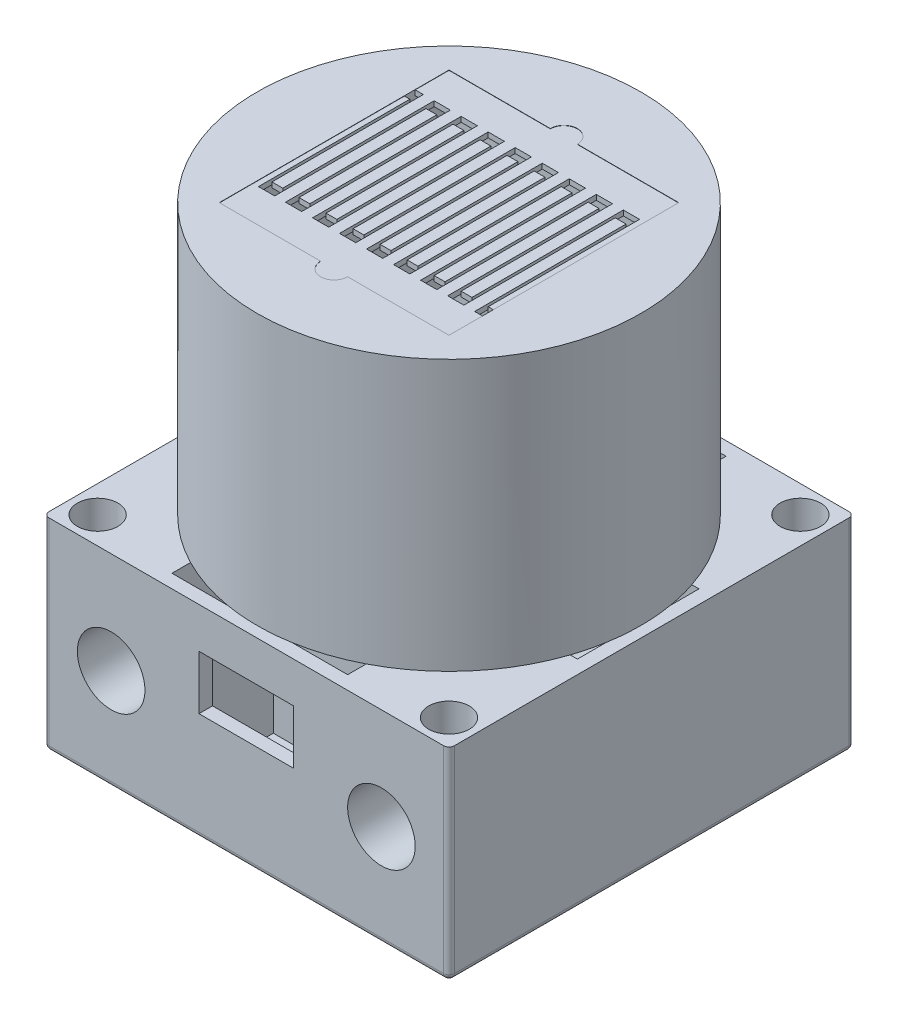
SolidWorks part; units mm, degrees
note: The reader was unsure of these and kept them because the rebuilt part matched: shared geometry of "草图9<2>".
ref_plane "前视基准面" through (0, 0, 0) normal (0, 0, 1) x (1, 0, 0)
ref_plane "上视基准面" through (0, 0, 0) normal (0, 1, 0) x (1, 0, 0)
ref_plane "右视基准面" through (0, 0, 0) normal (1, 0, 0) x (0, 0, -1)
sketch "草图2" plane through (0, 0, 0) normal (0, 1, 0) x (1, 0, 0)
  line L1 (-7.5, -7.5) -> (7.5, -7.5)
  line L2 (-7.5, -7.5) -> (-7.5, 7.5)
  line L3 (-7.5, 7.5) -> (7.5, 7.5)
  line L4 (7.5, -7.5) -> (7.5, 7.5)
extrude "凸台-拉伸1" add sketch "草图2" along normal blind 7.5
sketch "草图3" plane through (0, 7.5, 0) normal (0, 1, 0) x (-1, 0, 0)
  line L1 (7, 2.25) -> (-7, 2.25)
  line L2 (7, 2.25) -> (7, -2.25)
  line L3 (7, -2.25) -> (-7, -2.25)
  line L4 (-7, 2.25) -> (-7, -2.25)
extrude "切除-拉伸1" cut sketch "草图3" against normal blind 7
sketch "草图4" plane through (0, 7.5, 0) normal (0, 1, 0) x (1, 0, 0)
  circle A0 centre (0, 0) radius 3
extrude "切除-拉伸2" cut sketch "草图4" against normal blind 4.5
sketch "草图5" plane through (0, 7.5, 0) normal (0, 1, 0) x (-1, 0, 0)
  line L0 (7.9075, 0) -> (-8.3479, 0) construction
  line L1 (3.25, -3.25) -> (-3.25, -3.25)
  line L2 (3.25, -3.25) -> (3.25, -7)
  line L3 (3.25, -7) -> (-3.25, -7)
  line L4 (-3.25, -3.25) -> (-3.25, -7)
  line L5 (-3.25, 3.25) -> (-3.25, 7)
  line L6 (3.25, 7) -> (-3.25, 7)
  line L7 (3.25, 3.25) -> (3.25, 7)
  line L8 (3.25, 3.25) -> (-3.25, 3.25)
extrude "切除-拉伸3" cut sketch "草图5" against normal blind 7
sketch "草图6" plane through (0, 0, 7.5) normal (0, 0, 1) x (1, 0, 0)
  circle A0 centre (-5, 3.75) radius 1.5
  circle A1 centre (5, 3.75) radius 1.5
extrude "凸台-拉伸2" add sketch "草图6" against normal through all
sketch "草图7" plane through (0, 0, 7.5) normal (0, 0, 1) x (1, 0, 0)
  circle A0 centre (-5, 3.75) radius 1.25
  circle A1 centre (5, 3.75) radius 1.25
extrude "切除-拉伸4" cut sketch "草图7" against normal through all
sketch "草图8" plane through (0, 0, 0) normal (0, -1, 0) x (1, 0, 0)
  line L1 (-1.5, -1.5) -> (1.5, -1.5)
  line L2 (-1.5, -1.5) -> (-1.5, 1.5)
  line L3 (-1.5, 1.5) -> (1.5, 1.5)
  line L4 (1.5, -1.5) -> (1.5, 1.5)
extrude "凸台-拉伸3" add sketch "草图8" along normal blind 1
sketch "草图9" plane through (0, 0, 7.5) normal (0, 0, 1) x (1, 0, 0)
  line L1 (-1.75, 6) -> (1.75, 6)
  line L2 (-1.75, 6) -> (-1.75, 4)
  line L3 (-1.75, 4) -> (1.75, 4)
  line L4 (1.75, 6) -> (1.75, 4)
extrude "切除-拉伸5" cut sketch "草图9" against normal up to next
extrude "切除-拉伸6" cut sketch "草图9<2>" along normal up to next from offset 15 offset against normal yes
sketch "草图9<2>" plane through (0, 0, 7.5) normal (0, 0, 1) x (1, 0, 0) same geometry as "草图9"
sketch "草图10" plane through (0, 0, 0) normal (0, 0, 1) x (1, 0, 0)
  line L0 (-1.95, -2.5) -> (1.95, -2.5)
  line L1 (-1.95, -2.5) -> (-1.95, -1.5556)
  line L2 (1.95, -2.5) -> (1.95, -1.5556)
  line L4 (-1.5, -1) -> (-1.5, 0) construction
  line L5 (-1.5, -0.6771) -> (1.5, -0.6771)
  arc A0 (-1.5, -0.6771) -> (-1.95, -1.5556) centre (0, -2) ccw
  arc A3 (1.95, -1.5556) -> (1.5, -0.6771) centre (0, -2) ccw
extrude "凸台-拉伸4" add sketch "草图10" along normal blind 2 and the other way blind 2
sketch "草图11" plane through (0, 0, 0) normal (1, 0, 0) x (0, 0, -1)
  line L0 (1.95, -2.5) -> (1.95, -1.5556)
  line L1 (-1.95, -2.5) -> (-1.95, -1.5556)
  line L2 (2, -2.5) -> (1.95, -2.5)
  line L3 (-2, -2.5) -> (-2, -0.6771)
  line L4 (-2, -0.6771) -> (-1.5, -0.6771)
  line L5 (2, -0.6771) -> (2, -2.5)
  line L6 (-1.95, -2.5) -> (-2, -2.5)
  line L7 (1.5, -0.6771) -> (2, -0.6771)
  arc A0 (-1.5, -0.6771) -> (-1.95, -1.5556) centre (0, -2) ccw
  arc A1 (1.95, -1.5556) -> (1.5, -0.6771) centre (0, -2) ccw
extrude "切除-拉伸7" cut sketch "草图11" against normal up to next and the other way up to next
fillet "圆角1" radius 0.1 4 edges at (0, -2.5, -1.95) (-1.95, -2.5, 0) (0, -2.5, 1.95) (1.95, -2.5, 0)
fillet "圆角2" radius 0.2 8 edges at (-7.5, 3.75, -7.5) (7.5, 3.75, -7.5) (-7.5, 3.75, 7.5) (-7.5, 0, 0) (0, 0, -7.5) (7.5, 0, 0) (0, 0, 7.5) (7.5, 3.75, 7.5)
sketch "草图12" plane through (0, 7.5, 0) normal (0, 1, 0) x (-1, 0, 0)
  circle A0 centre (6.5, -6.5) radius 0.75
  circle A1 centre (-6.5, 6.5) radius 0.75
  circle A2 centre (6.5, 6.5) radius 0.75
  circle A3 centre (-6.5, -6.5) radius 0.75
extrude "切除-拉伸8" cut sketch "草图12" against normal blind 2
sketch "草图13" plane through (0, 7.5, 0) normal (0, 1, 0) x (-1, 0, 0)
  line L1 (5.75, -2) -> (-5.75, -2)
  line L2 (5.75, -2) -> (5.75, 2)
  line L3 (5.75, 2) -> (-5.75, 2)
  line L4 (-5.75, -2) -> (-5.75, 2)
extrude "凸台-拉伸5" add sketch "草图13" against normal blind 1 separate body
sketch "草图14" plane through (0, 7.5, 0) normal (0, 1, 0) x (-1, 0, 0)
  circle A0 centre (0, 0) radius 2.9
extrude "凸台-拉伸6" add sketch "草图14" against normal blind 4
sketch "草图15" plane through (0, 7.5, 0) normal (0, 1, 0) x (-1, 0, 0)
  circle A0 centre (0, 0) radius 2.5
extrude "切除-拉伸9" cut sketch "草图15" against normal blind 3.5
sketch "草图16" plane through (0, 0, 0) normal (0, 0, 1) x (1, 0, 0)
  line L0 (0, -0.4478) -> (0, 7.9679) construction
  line L2 (0, 4) -> (1.5, 4)
  line L3 (0, 4) -> (0, 7.5)
  line L5 (1.5, 4) -> (1.5, 6.0006)
  arc A0 (1.5, 6) -> (0, 7.5) centre (0, 6) ccw
revolve "旋转2" add sketch "草图16" angle 360 about L0
sketch "草图19" plane through (0, 7.5, 0) normal (0, 1, 0) x (1, 0, 0)
  line L0 (4.25, 4.25) -> (4.25, -4.25)
  line L1 (4.25, 4.25) -> (-4.25, 4.25)
  line L2 (4.25, -4.25) -> (-4.25, -4.25)
  line L3 (-4.25, 4.25) -> (-4.25, -4.25)
  line L4 (4.25, 4.25) -> (-4.25, -4.25) construction
  line L5 (4.25, -4.25) -> (-4.25, 4.25) construction
  circle A0 centre (0, 0) radius 7.1
  dimension "D1" = 14.2
  dimension "D2" = 8.5
  dimension "D3" = 8.5
extrude "凸台-拉伸11" add sketch "草图19" along normal blind 10
sketch "草图20" plane through (0, 17.5, 0) normal (0, 1, 0) x (1, 0, 0)
  line L0 (4.25, 4.25) -> (4.25, -4.25)
  line L1 (4.25, 4.25) -> (-4.25, 4.25)
  line L2 (4.25, -4.25) -> (-4.25, -4.25)
  line L3 (-4.25, 4.25) -> (-4.25, -4.25)
  line L4 (4.25, 4.25) -> (-4.25, -4.25) construction
  line L5 (4.25, -4.25) -> (-4.25, 4.25) construction
  point P1 (0, 0)
  dimension "D1" = 8.5
  dimension "D2" = 8.5
extrude "凸台-拉伸12" add sketch "草图20" against normal blind 0.2
sketch "草图22" plane through (0, 17.5, 0) normal (0, 1, 0) x (1, 0, 0)
  line L0 (0, 0) -> (-4.25, 0) construction
  line L1 (-4.25, 0) -> (-4.25, 3) construction
  line L2 (-4.25, 3) -> (-4.25, 2.6)
  line L3 (-4.25, 3) -> (-3.95, 3)
  line L4 (-4.25, 2.6) -> (-4.05, 2.6)
  line L5 (-3.95, 3) -> (-3.95, 2.6)
  line L6 (-3.95, 2.6) -> (-3.95, -2.6)
  line L7 (-3.45, 2.6) -> (-3.25, 2.6)
  line L8 (-3.95, -2.6) -> (-3.55, -2.6)
  line L9 (-4.05, 2.6) -> (-4.05, -2.6)
  line L10 (-4.05, -2.6) -> (-4.05, -3)
  line L12 (-4.05, -3) -> (-3.45, -3)
  line L13 (-3.45, -2.6) -> (-3.45, -3)
  line L15 (-3.45, -2.6) -> (-3.45, 2.6)
  line L16 (-3.55, -2.6) -> (-3.55, 2.6)
  line L18 (-3.55, 2.6) -> (-3.55, 3)
  line L20 (-3.55, 3) -> (-3.25, 3)
  line L21 (-3.25, 2.6) -> (-3.25, 3)
  dimension "D1" = 4.25
  dimension "D2" = 3
  dimension "D3" = 0.3
  dimension "D4" = 0.4
  dimension "D5" = 5.2
  dimension "D6" = 0.1
  dimension "D7" = 0.4
  dimension "D8" = 0.6
  dimension "D9" = 5.2
  dimension "D10" = 0.1
  dimension "D11" = 0.3
  dimension "D12" = 0.4
extrude "切除-拉伸10" cut sketch "草图22" against normal blind 0.2
pattern_linear "阵列(线性)1" count 8 spacing 1 along (1, 0, 0) of "切除-拉伸10"
sketch "草图23" plane through (0, 17.5, 0) normal (0, 1, 0) x (1, 0, 0)
  line L0 (3.75, 3) -> (3.75, 2.6)
  line L1 (3.75, 3) -> (4.05, 3)
  line L2 (3.75, 2.6) -> (3.95, 2.6)
  line L3 (4.05, 3) -> (4.05, 2.6)
  line L5 (4.05, 2.6) -> (4.05, -2.6)
  line L6 (3.95, 2.6) -> (3.95, -2.6)
  line L8 (3.95, -2.6) -> (3.95, -3)
  line L9 (4.05, -2.6) -> (4.25, -2.6)
  line L10 (3.95, -3) -> (4.25, -3)
  line L11 (4.25, -2.6) -> (4.25, -3)
  dimension "D1" = 0.3
  dimension "D2" = 5.2
  dimension "D3" = 0.1
  dimension "D4" = 0.4
  dimension "D5" = 0.3
extrude "切除-拉伸12" cut sketch "草图23" against normal blind 0.2
sketch "草图25" plane through (0, 17.5, 0) normal (0, 1, 0) x (1, 0, 0)
  line L0 (4.25, 4.25) -> (0.5, 4.25)
  line L1 (4.25, 4.25) -> (4.25, -4.25)
  line L2 (-4.25, 4.25) -> (-4.25, -4.25)
  line L3 (4.25, -4.25) -> (0.5, -4.25)
  line L4 (4.25, 4.25) -> (-4.25, -4.25) construction
  line L5 (-4.25, 4.25) -> (4.25, -4.25) construction
  line L6 (-0.5, 4.25) -> (-4.25, 4.25)
  line L7 (-0.5, -4.25) -> (-4.25, -4.25)
  arc A0 (0.5, 4.25) -> (-0.5, 4.25) centre (0, 4.25) ccw
  arc A1 (-0.5, -4.25) -> (0.5, -4.25) centre (0, -4.25) ccw
  point P2 (0, 0)
  dimension "D3" = 1
  dimension "D4" = 1
  dimension "D1" = 8.5
  dimension "D2" = 8.5
extrude "切除-拉伸13" cut sketch "草图25" against normal blind 0.01
